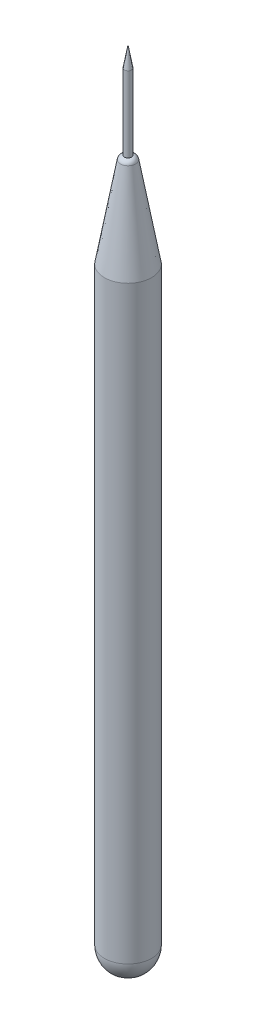
SolidWorks part; units mm, degrees
material "TIMETAL 35A CP Titanium (ASTM Grade 1) 99.1 Ti"
ref_plane "Front Plane" through (0, 0, 0) normal (0, 0, 1) x (1, 0, 0)
ref_plane "Top Plane" through (0, 0, 0) normal (0, 1, 0) x (1, 0, 0)
ref_plane "Right Plane" through (0, 0, 0) normal (1, 0, 0) x (0, 0, -1)
sketch "Sketch1" plane through (0, 0, 0) normal (0, 1, 0) x (1, 0, 0)
  circle A0 centre (0, 0) radius 5
  dimension "D1" = 10
extrude "Boss-Extrude1" add sketch "Sketch1" along normal mid plane 150
chamfer "Chamfer1" distance 20 angle 10 1 edges at (0, 75, 5) first distance on face at (0, 75, 5)
fillet "Fillet1" radius 5 1 edges at (0, -75, 5)
sketch "Sketch2" plane through (0, 75, 0) normal (0, 1, 0) x (1, 0, 0)
  circle A0 centre (0, 0) radius 0.75
  dimension "D1" = 1.5
extrude "Boss-Extrude2" add sketch "Sketch2" along normal blind 20
chamfer "Chamfer2" distance 4 angle 10 1 edges at (0, 95, 0.75) first distance on face at (0, 95, 0.75)
fillet "Fillet2" radius 1 1 edges at (0, 75, 1.4735)
ref_point "Point1"
